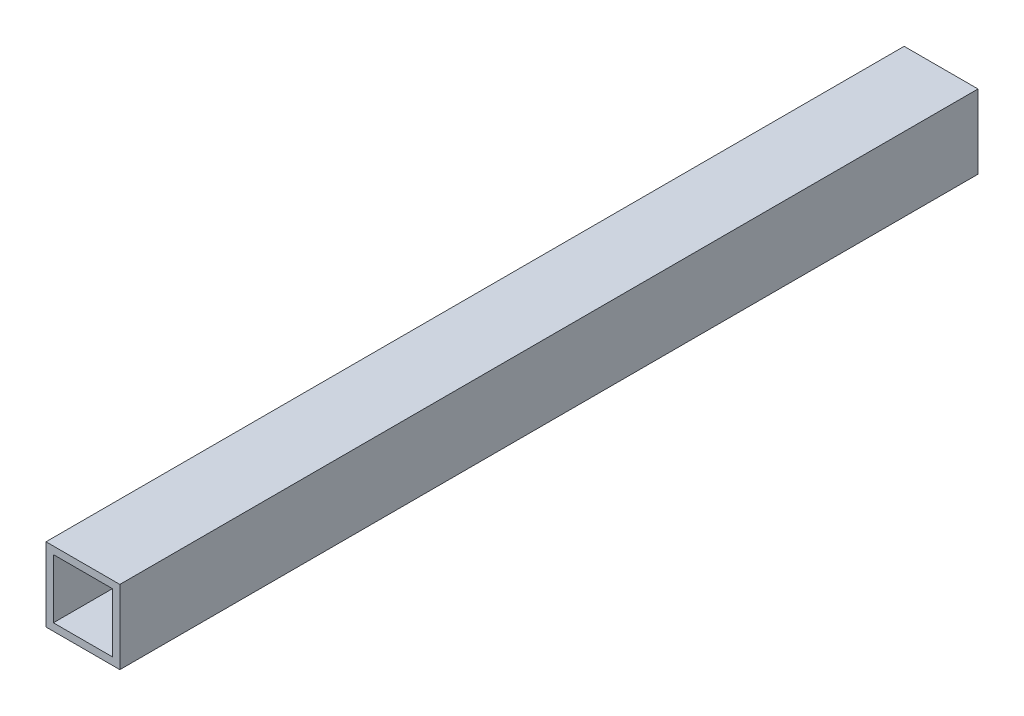
SolidWorks part; units mm, degrees
ref_plane "Front Plane" through (0, 0, 0) normal (0, 0, 1) x (1, 0, 0)
ref_plane "Top Plane" through (0, 0, 0) normal (0, 1, 0) x (1, 0, 0)
ref_plane "Right Plane" through (0, 0, 0) normal (1, 0, 0) x (0, 0, -1)
sketch "Sketch1" plane through (0, 0, 0) normal (0, 0, 1) x (1, 0, 0)
  line L1 (0, 20) -> (20, 20)
  line L2 (0, 20) -> (0, 0)
  line L3 (0, 0) -> (20, 0)
  line L4 (20, 20) -> (20, 0)
  dimension "D1" = 20
extrude "Extrude-Thin1" add sketch "Sketch1" along normal blind 232.4 thin thin type one direction reverse wall 2
